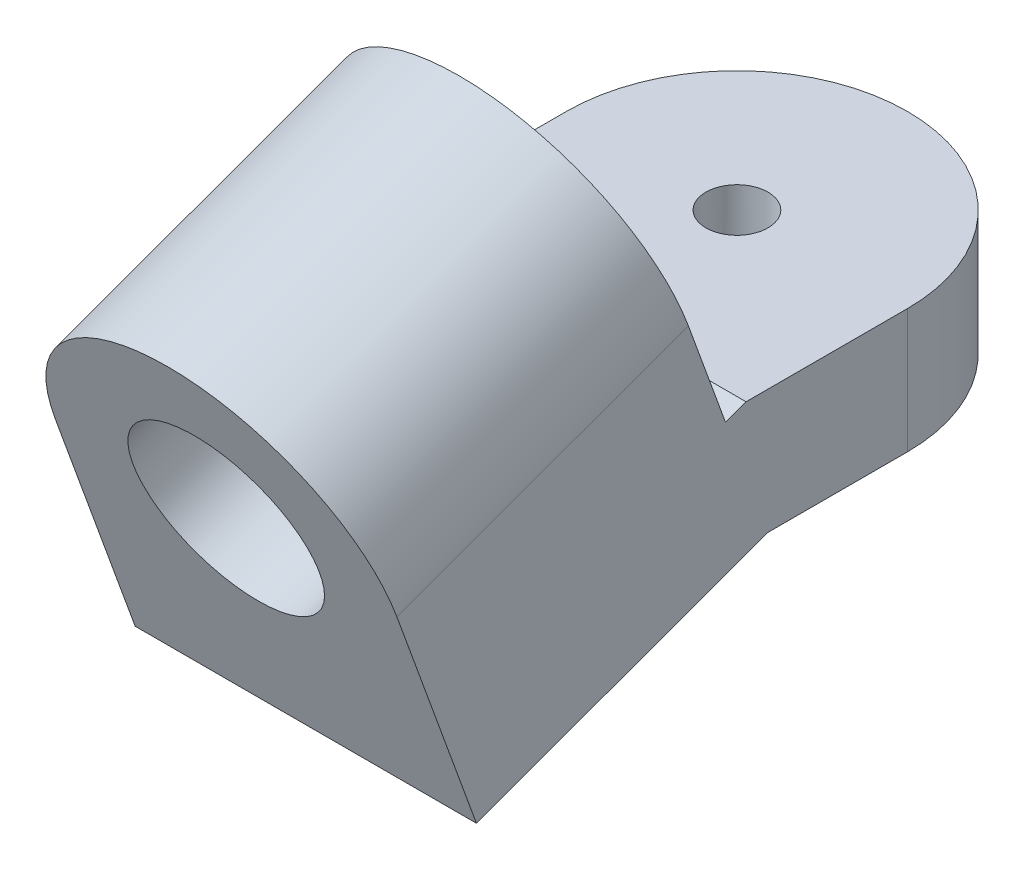
SolidWorks part; units mm, degrees
material "3D printed plastic"
ref_plane "Front Plane" through (0, 0, 0) normal (0, 0, 1) x (1, 0, 0)
ref_plane "Top Plane" through (0, 0, 0) normal (0, 1, 0) x (1, 0, 0)
ref_plane "Right Plane" through (0, 0, 0) normal (1, 0, 0) x (0, 0, -1)
sketch "Sketch2" plane through (0, 0, 0) normal (1, 0, 0) x (0, 0, -1)
  line L0 (0, 0) -> (-10, 0)
  line L1 (-10, 0) -> (-19.3969, -3.4202)
  dimension "D1" = 10
  dimension "D2" = 20
  dimension "D3" = 10
extrude "Extrude-Thin1" add sketch "Sketch2" along normal mid plane 11 thin thin type one direction wall 4
fillet "Fillet1" radius 5.5 2 edges at (-5.5, 2, 0) (5.5, 2, 0)
sketch "Sketch3" plane through (0, 4, 0) normal (0, 1, 0) x (1, 0, 0)
  circle A0 centre (0, -5.5) radius 1
  dimension "D1" = 2
extrude "Cut-Extrude1" cut sketch "Sketch3" against normal through all
sketch "Sketch4" plane through (0, 0, 0) normal (0, -1, 0) x (1, 0, 0)
  circle A0 centre (0, 5.5) radius 2.25
  dimension "D1" = 4.5
extrude "Cut-Extrude2" cut sketch "Sketch4" against normal blind 2
sketch "Sketch5" plane through (0, -6.6341, 18.2271) normal (0, -0.342, 0.9397) x (1, 0, 0)
  line L0 (0, 10.9202) -> (0, 3.4202) construction
  line L1 (5.5, 3.4202) -> (-5.5, 3.4202) construction
  line L2 (-5.5, 7.4202) -> (5.5, 7.4202) construction
  line L3 (5.5, 7.4202) -> (5.5, 10.9202)
  line L4 (-5.5, 10.9202) -> (-5.5, 7.4202)
  line L5 (5.5, 7.4202) -> (-5.5, 7.4202) construction
  line L6 (5.5, 7.4202) -> (5.5, 3.4202)
  line L7 (5.5, 3.4202) -> (-5.5, 3.4202)
  line L9 (-5.5, 3.4202) -> (-5.5, 7.4202)
  circle A0 centre (0, 10.9202) radius 3
  arc A1 (5.5, 10.9202) -> (-5.5, 10.9202) centre (0, 10.9202) ccw
  dimension "D1" = 6
  dimension "D2" = 7.5
  dimension "D3" = 11
extrude "Boss-Extrude1" add sketch "Sketch5" against normal blind 10
sketch "Sketch6" plane through (0, -3.2139, 8.8302) normal (0, 0.342, -0.9397) x (-1, 0, 0)
  circle A0 centre (0, 10.9202) radius 1
  dimension "D1" = 2
extrude "Boss-Extrude2" [suppressed] add sketch "Sketch6" along normal blind 500 separate body
